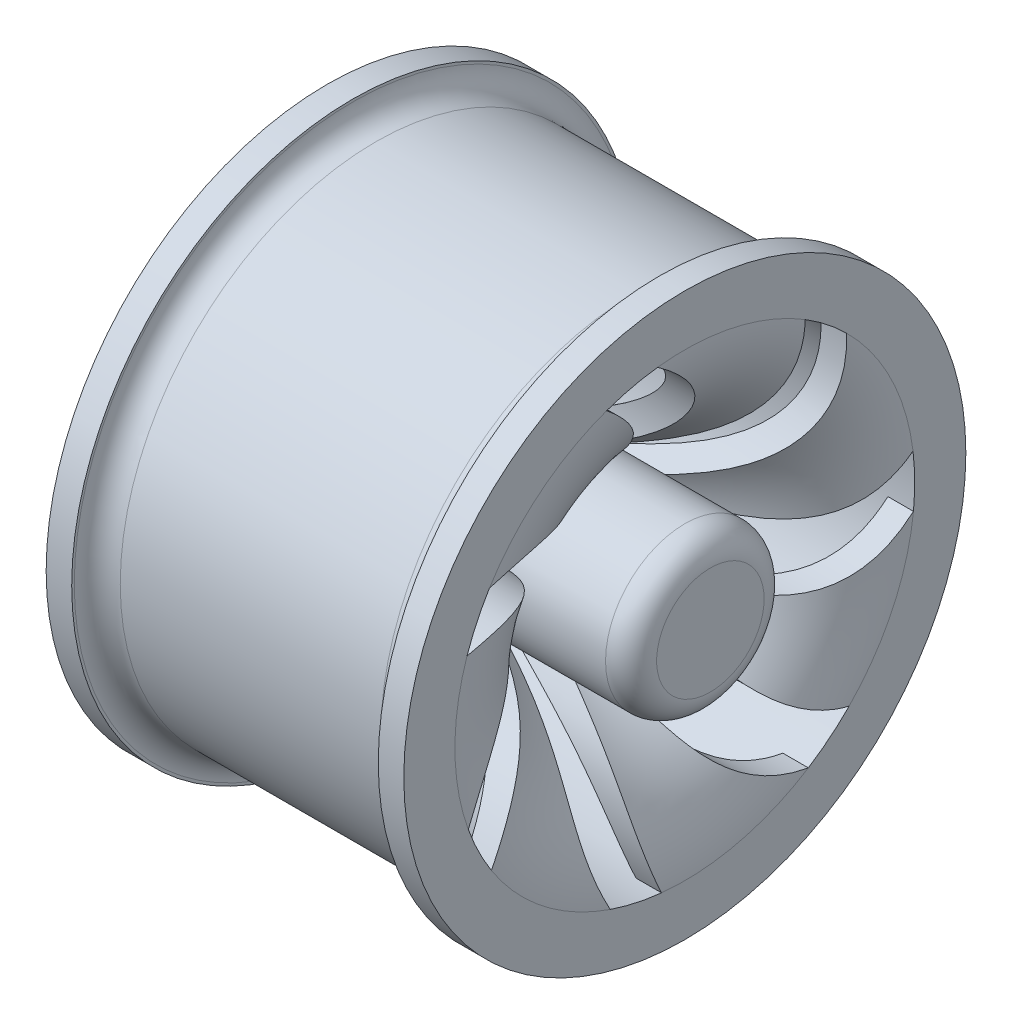
SolidWorks part; units mm, degrees
material "AISI 1020 Steel, Cold Rolled"
ref_plane "Front Plane" through (0, 0, 0) normal (0, 0, 1) x (1, 0, 0)
ref_plane "Top Plane" through (0, 0, 0) normal (0, 1, 0) x (1, 0, 0)
ref_plane "Right Plane" through (0, 0, 0) normal (1, 0, 0) x (0, 0, -1)
sketch "Sketch1" plane through (0, 0, 0) normal (0, 0, 1) x (1, 0, 0)
  line L0 (0, 0) -> (250.7524, 0) construction
  line L1 (0, 0) -> (0, 330.2935) construction
  line L2 (-177.8, 228.6) -> (152.4, 228.6)
  line L3 (177.8, 228.6) -> (177.8, 279.4)
  line L4 (177.8, 279.4) -> (152.4, 279.4)
  line L5 (152.4, 279.4) -> (152.4, 276.86)
  line L6 (129.54, 254) -> (-129.54, 254)
  line L7 (-152.4, 279.4) -> (-152.4, 276.86)
  line L8 (-177.8, 279.4) -> (-152.4, 279.4)
  line L9 (-177.8, 228.6) -> (-177.8, 279.4)
  line L10 (177.8, 192.1475) -> (177.8, 265.0525) construction
  line L11 (0, 50.8) -> (0, 78.8369)
  arc A0 (152.4, 276.86) -> (129.54, 254) centre (129.54, 276.86) cw
  arc A1 (-152.4, 276.86) -> (-129.54, 254) centre (-129.54, 276.86) ccw
  spline S0 degree 3 poles (177.8, 228.6) (177.8, 128.8585) (68.6539, 83.0638) (0, 50.8) knots 0 0 0 0 1 1 1 1
  spline S1 degree 1 poles (152.4, 228.6) (-10.8032, 73.7881) knots 0 0 1 1 construction
  spline S2 degree 3 poles (152.4, 228.6) (152.4, 227.3456) (152.3566, 224.8166) (152.1021, 219.9254) (151.4798, 213.9972) (150.2746, 207.1817) (148.0852, 198.4326) (144.2986, 188.0506) (138.1557, 176.2633) (130.4699, 165.0262) (118.2776, 150.7159) (99.6867, 134.0822) (77.8278, 119.1945) (59.2531, 108.2991) (45.0007, 100.6058) (30.6471, 93.3553) (18.7803, 87.6441) (9.4473, 83.2463) (4.2682, 80.8271) (0.8542, 79.2351) (-1.4063, 78.1813) (-4.2028, 76.8776) (-7.5266, 75.3252) (-9.7082, 74.3026) (-10.8032, 73.7881) knots 0 0 0 0 0.015625 0.03125 0.0625 0.09375 0.125 0.1875 0.25 0.3125 0.375 0.5 0.625 0.6875 0.75 0.8125 0.875 0.90625 0.9375 0.945407 0.95322 0.96875 0.984375 1 1 1 1 only from (152.4, 228.6) to (0, 78.8369)
  point P4 (0, 254)
  point P12 (152.4, 254)
  point P19 (0, 228.6)
  dimension "D5" = 22.86
  dimension "D1" = 25.4
  dimension "D2" = 50.8
  dimension "D3" = 177.8
  dimension "D4" = 25.4
  dimension "D6" = 254
  dimension "D7" = 50.8
  dimension "D8" = 127
  dimension "D9" = 25.4
revolve "Revolve1" add sketch "Sketch1" angle 360 about L0
sketch "Sketch2" plane through (-177.8, 0, 0) normal (-1, 0, 0) x (0, 0, 1)
  circle A0 centre (0, 0) radius 50.8 construction
  circle A1 centre (0, 0) radius 50.8
  circle A2 centre (0, 0) radius 78.8369 construction
  circle A3 centre (0, 0) radius 78.8369
extrude "Boss-Extrude1" add sketch "Sketch2" against normal blind 330.2
sketch "Sketch3" plane through (152.4, 0, 0) normal (1, 0, 0) x (0, 0, -1)
  circle A0 centre (0, 0) radius 78.8369 construction
  circle A1 centre (0, 0) radius 78.8369
extrude "Boss-Extrude2" add sketch "Sketch3" along normal blind 50.8
sketch "Sketch4" plane through (177.8, 0, 0) normal (1, 0, 0) x (0, 0, -1)
  circle A0 centre (0, 0) radius 78.8369 construction
  arc A1 (27.8061, 73.7705) -> (-27.8061, 73.7705) centre (0, 0) ccw
  circle A2 centre (0, 0) radius 228.6 construction
  arc A3 (-26.9903, 227.0011) -> (-77.7903, 214.9573) centre (0, 0) ccw
  spline S0 degree 2 poles (-77.7903, 214.9573) (-7.896, 157.8287) (-27.8061, 73.7705) knots 0 0 0 1 1 1
  spline S1 degree 2 poles (27.8061, 73.7705) (55.7067, 167.956) (-26.9903, 227.0011) knots 0 0 0 1 1 1
  dimension "3.75" = 50.8
extrude "Cut-Extrude2" cut sketch "Sketch4" against normal through all
pattern_circular "CirPattern1" count 7 over 360 about axis through (203.2, 0, 0) along (1, 0, 0) of "Cut-Extrude2"
fillet "Fillet1" radius 25.4 1 edges at (203.2, 0, -78.8369)
ref_plane "Plane1" through (0, 0, 0) normal (-1, 0, 0) x (0, 0, 1)
